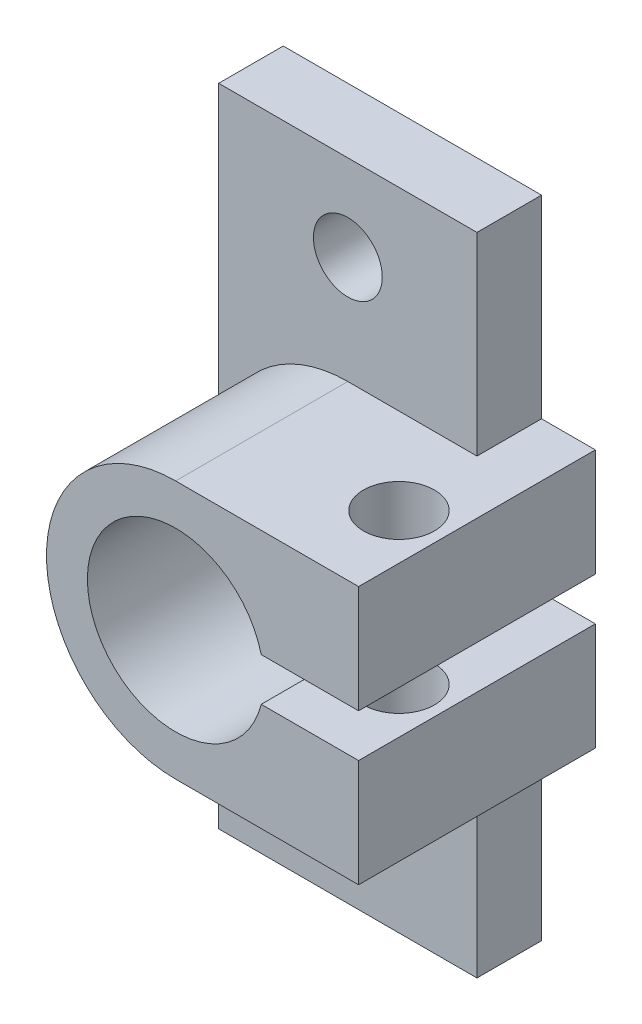
SolidWorks part; units mm, degrees
ref_plane "Plano frontal" through (0, 0, 0) normal (0, 0, 1) x (1, 0, 0)
ref_plane "Plano superior" through (0, 0, 0) normal (0, 1, 0) x (1, 0, 0)
ref_plane "Plano direito" through (0, 0, 0) normal (1, 0, 0) x (0, 0, -1)
sketch "Esboço1" plane through (0, 0, 0) normal (0, 0, 1) x (1, 0, 0)
  line L0 (-6, 15) -> (-6, -15)
  line L1 (6, -15) -> (6, -1)
  line L2 (0, 0) -> (6, 0) construction
  line L3 (3.9762, -1) -> (6, -1)
  line L4 (3.9762, 1) -> (6, 1)
  line L5 (0, 1) -> (6, 1) construction
  line L6 (0, -1) -> (6, -1) construction
  line L7 (6, 1) -> (6, 15)
  line L8 (-6, 15) -> (6, 15)
  line L9 (6, -15) -> (-6, -15)
  arc A0 (3.9762, 1) -> (3.9762, -1) centre (0, 0) ccw
  circle A1 centre (0, 11) radius 1.6
  circle A2 centre (0, -11) radius 1.6
  point P1 (0, 0)
  point P7 (0, 15)
  point P19 (0, 12.5786)
  dimension "D1" = 12
  dimension "D2" = 3.2
  dimension "D3" = 8.2
  dimension "D4" = 30
  dimension "D7" = 22
  dimension "D5" = 1
  dimension "D6" = 1
extrude "Ressalto-extrusão1" add sketch "Esboço1" along normal blind 3
sketch "Esboço2" plane through (0, 0, 3) normal (0, 0, 1) x (1, 0, 0)
  line L0 (8.5, 6) -> (8.5, 1)
  line L1 (6, -15) -> (6, -1) construction
  line L2 (8.5, 6) -> (0, 6)
  line L3 (8.5, -1) -> (8.5, -6)
  line L5 (-6, 15) -> (-6, -15)
  line L6 (6, -15) -> (6, -1)
  line L7 (6, -1) -> (3.9762, -1)
  line L8 (3.9762, 1) -> (6, 1)
  line L9 (6, 1) -> (6, 15)
  line L10 (8.5, -6) -> (0, -6)
  line L11 (0, 0) -> (11.2942, 0) construction
  line L12 (8.5, -1) -> (3.9762, -1)
  line L13 (3.9762, 1) -> (8.5, 1)
  line L20 (6, 15) -> (-6, 15)
  line L21 (6, 15) -> (-6, 15)
  line L22 (-6, -15) -> (6, -15)
  line L23 (-6, -15) -> (6, -15)
  arc A0 (0, -6) -> (0, 6) centre (0, 0) cw
  arc A5 (3.9762, 1) -> (3.9762, -1) centre (0, 0) ccw
  arc A8 (3.9762, 1) -> (3.9762, -1) centre (0, 0) ccw
  line M18 (6, -15) -> (6, -1)
  line M19 (6, -1) -> (3.9762, -1)
  arc M20 (3.9762, -1) -> (3.9762, 1) centre (0, 0) cw
  line M21 (3.9762, 1) -> (6, 1)
  line M22 (6, 1) -> (6, 15)
  dimension "D2" = 6
  dimension "D3" = 2.5
  dimension "D1" = 0
extrude "Ressalto-extrusão2" add sketch "Esboço2" along normal blind 8 and the other way through all contours A0 L10 L2 M18 M19 M20 M21 M22 | L13 L0 L2 M22 | L3 L12 L10 M18 region at (7.25, 3.5, 3) region at (5.8303, 3.5, 3) region at (7.25, -3.5, 3)
sketch "Esboço3" plane through (0, 1, 0) normal (0, -1, 0) x (1, 0, 0)
  line L0 (3.9762, 11) -> (3.9762, 3) construction
  line L1 (3.9762, 11) -> (3.9762, 0) construction
  line L2 (-6, 3) -> (8.5, 3) construction
  line L3 (8.5, 0) -> (8.5, 11) construction
  line L4 (-6, 3) -> (-6, 0) construction
  circle A0 centre (6.3762, 7) radius 1.65
  point P7 (-8.0258, 2.6495)
  point P13 (3.9762, 7)
  point P14 (0, 0)
  point P15 (0, 0)
  point P18 (3.9762, 11)
  point P20 (6.3762, 7.1443)
  point P21 (-7.5, 3)
  point P22 (6.3762, 8.2963)
  point P23 (0, 0)
  dimension "D1" = 3.3
  dimension "D2" = 2.4
extrude "Corte-extrusão1" cut sketch "Esboço3" against normal through all both and the other way through all
